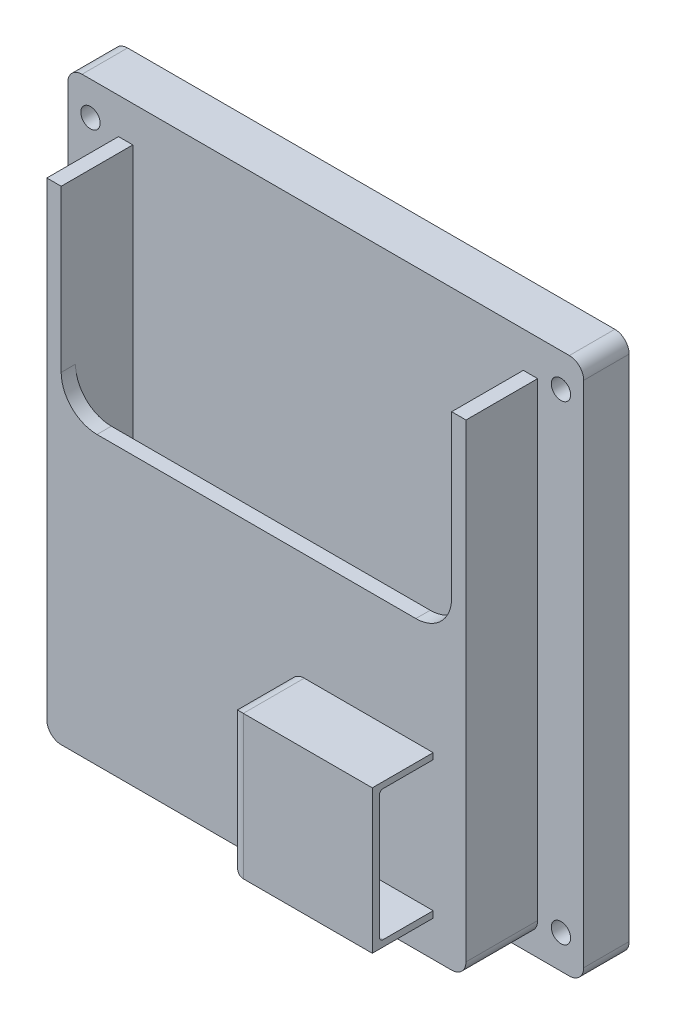
SolidWorks part; units mm, degrees
ref_plane "Front Plane" through (0, 0, 0) normal (0, 0, 1) x (1, 0, 0)
ref_plane "Top Plane" through (0, 0, 0) normal (0, 1, 0) x (1, 0, 0)
ref_plane "Right Plane" through (0, 0, 0) normal (1, 0, 0) x (0, 0, -1)
sketch "Sketch1" plane through (0, 0, 0) normal (0, 0, 1) x (1, 0, 0)
  line L0 (0, 0) -> (0, 37.5) construction
  line L1 (-36, 37.5) -> (36, 37.5)
  line L2 (-36, 37.5) -> (-36, -37.5)
  line L3 (-36, -37.5) -> (36, -37.5)
  line L4 (36, 37.5) -> (36, -37.5)
  line L5 (-36, 37.5) -> (36, -37.5) construction
  line L6 (-36, -37.5) -> (36, 37.5) construction
  line L7 (0, 0) -> (36, 0) construction
  circle A0 centre (-32.83, 32.83) radius 1.35
  circle A1 centre (-32.83, -32.83) radius 1.35
  circle A2 centre (32.83, 32.83) radius 1.35
  circle A3 centre (32.83, -32.83) radius 1.35
  point P0 (0, 0)
  dimension "D5" = 2.7
  dimension "D1" = 72
  dimension "D2" = 75
  dimension "D3" = 65.66
  dimension "D4" = 65.66
extrude "Boss-Extrude1" add sketch "Sketch1" along normal blind 6.35
sketch "Sketch2" plane through (0, 0, 6.35) normal (0, 0, 1) x (1, 0, 0)
  line L0 (0, 0) -> (0, 37.5) construction
  line L1 (36, 37.5) -> (-36, 37.5) construction
  line L2 (0, 0) -> (36, 0) construction
  line L3 (36, -37.5) -> (36, 37.5) construction
  line L4 (-32.83, 32.83) -> (-32.83, -32.83) construction
  line L5 (-28.92, 32.5) -> (-26.92, 32.5)
  line L6 (-28.92, 32.5) -> (-28.92, -32.5)
  line L7 (-28.92, -32.5) -> (-26.92, -32.5)
  line L8 (-26.92, 32.5) -> (-26.92, -32.5)
  line L9 (27.58, 32.5) -> (29.58, 32.5)
  line L10 (27.58, 32.5) -> (27.58, -32.5)
  line L11 (27.58, -32.5) -> (29.58, -32.5)
  line L12 (29.58, 32.5) -> (29.58, -32.5)
  line L13 (32.83, -32.83) -> (32.83, 32.83) construction
  line L15 (-28.92, -32.5) -> (29.58, -32.5)
  line L16 (-28.92, -32.5) -> (-28.92, -35)
  line L17 (-28.92, -35) -> (29.58, -35)
  line L18 (29.58, -32.5) -> (29.58, -35)
  dimension "D1" = 2.5
  dimension "D2" = 3.25
  dimension "D3" = 2
  dimension "D4" = 2
  dimension "D6" = 65
  dimension "D7" = 58.5
extrude "Boss-Extrude2" add sketch "Sketch2" along normal blind 10 contours L12 L9 L10 L11 | L18 L11 L15 L7 L16 L17 | L6 L5 L8 L7 region at (0.33, -33.75, 6.35) region at (28.58, 0, 6.35)
sketch "Sketch3" plane through (0, 0, 16.35) normal (0, 0, 1) x (1, 0, 0)
  line L0 (29.58, 32.5) -> (29.58, -35) construction
  line L1 (-28.92, -35) -> (29.58, -35)
  line L2 (-28.92, -35) -> (-28.92, 5)
  line L3 (-28.92, 5) -> (29.58, 5)
  line L4 (29.58, -35) -> (29.58, 5)
  dimension "D1" = 40
extrude "Boss-Extrude3" add sketch "Sketch3" against normal blind 2
fillet "Fillet1" radius 5 2 edges at (-26.92, 5, 15.35) (27.58, 5, 15.35)
sketch "Sketch4" plane through (0, 0, 16.35) normal (0, 0, 1) x (1, 0, 0)
  line L0 (0, 0) -> (0, 37.5) construction
  line L1 (5, -10) -> (25, -10)
  line L2 (5, -10) -> (5, -30)
  line L3 (5, -30) -> (25, -30)
  line L4 (25, -10) -> (25, -30)
  line L5 (36, 37.5) -> (-36, 37.5) construction
  line L6 (0, 0) -> (36, 0) construction
  line L7 (36, -37.5) -> (36, 37.5) construction
  dimension "D1" = 10
  dimension "D2" = 5
  dimension "D3" = 20
  dimension "D4" = 20
extrude "Boss-Extrude4" add sketch "Sketch4" along normal blind 8.5
sketch "Sketch5" plane through (25, 0, 0) normal (1, 0, 0) x (0, 0, -1)
  line L0 (-16.35, -30) -> (-16.35, -10) construction
  line L1 (-16.35, -29.1) -> (-23.85, -29.1)
  line L2 (-16.35, -29.1) -> (-16.35, -10.85)
  line L3 (-16.35, -10.85) -> (-23.85, -10.85)
  line L4 (-23.85, -29.1) -> (-23.85, -10.85)
  line L5 (-24.85, -30) -> (-16.35, -30) construction
  dimension "D1" = 18.25
  dimension "D2" = 0.9
  dimension "D3" = 7.5
extrude "Cut-Extrude1" cut sketch "Sketch5" against normal blind 18.5
fillet "Fillet2" radius 0.5 2 edges at (15.75, -29.1, 23.85) (15.75, -10.85, 23.85)
fillet "Fillet3" radius 2 6 edges at (-36, 37.5, 3.175) (36, 37.5, 3.175) (29.58, -35, 11.35) (36, -37.5, 3.175) (-36, -37.5, 3.175) (-28.92, -35, 11.35)
fillet "Fillet4" radius 2 3 edges at (5, -20, 24.85) (5, -10, 20.6) (5, -30, 20.6)
